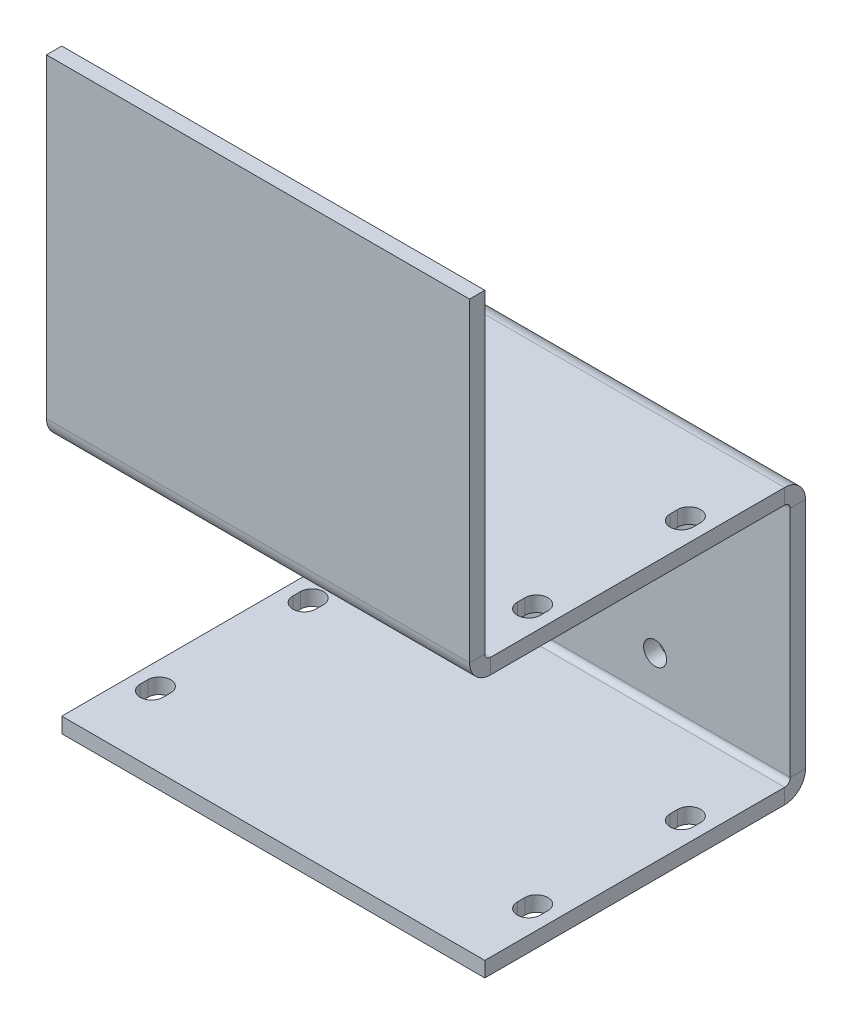
SolidWorks part; units mm, degrees
note: The reader was unsure of these and kept them because the rebuilt part matched: flange length of "Odgięcie krawędzi1", "Odgięcie krawędzi2".
ref_plane "Płaszczyzna przednia" through (0, 0, 0) normal (0, 0, 1) x (1, 0, 0)
ref_plane "Płaszczyzna górna" through (0, 0, 0) normal (0, 1, 0) x (1, 0, 0)
ref_plane "Płaszczyzna prawa" through (0, 0, 0) normal (1, 0, 0) x (0, 0, -1)
sketch "Szkic1" plane through (0, 0, 0) normal (0, 0, 1) x (1, 0, 0)
  line L1 (-27.7, -16) -> (27.7, -16)
  line L2 (-27.7, -16) -> (-27.7, 16)
  line L3 (-27.7, 16) -> (27.7, 16)
  line L4 (27.7, -16) -> (27.7, 16)
  line L5 (-27.7, -16) -> (27.7, 16) construction
  line L6 (-27.7, 16) -> (27.7, -16) construction
  point P0 (0, 0)
  dimension "D1" = 55.4
  dimension "D2" = 32
base flange "Odgięcie bazowe1" sketch "Szkic1" thickness 2 reverse thickness direction no parameters "D1"=0.7366
hole_wizard "Otwory ustalające Ø3.0mm1" positions "Szkic11" profile "Szkic12" hole size "Ø3.0" standard "Ansi Metric"
sketch "Szkic11" plane through (0, 0, -2) normal (0, 0, -1) x (-1, 0, 0)
  line L0 (0, 16) -> (0, -16) construction
  line L5 (-27.7, 0) -> (27.7, 0) construction
  line L6 (-27.7, -16) -> (-27.7, 16) construction
  line L7 (27.7, 16) -> (27.7, -16) construction
  line L11 (-27.7, 16) -> (27.7, 16) construction
  line L12 (27.7, -16) -> (-27.7, -16) construction
  point P0 (-10, 10)
  point P22 (10, 10)
  point P23 (10, -10)
  point P24 (-10, -10)
  dimension "D1" = 10
  dimension "D2" = 10
sketch "Szkic12" plane through (10, 10, -2) normal (1, 0, 0) x (0, 1, 0)
  line L0 (0, 0) -> (0, 17.9013)
  line L1 (0, 17.9013) -> (1.5, 17)
  line L2 (1.5, 17) -> (1.5, 0)
  line L5 (1.5, 0) -> (0, 0)
  line L10 (0, 17.9013) -> (-1.5, 17) construction
  line L11 (0, -6.35) -> (0, 107.95) construction
  dimension "Średnica otworu" = 3
  dimension "Głębokość otworu" = 17
  dimension "Kąt wiertła" = 118
edge flange "Odgięcie krawędzi1" sketch "Szkic8" flange profiles "Szkic8", "Szkic10" flange angle 90 flange length 42 flange position material outside bend radius 0.7366 thickness 2 relief rectangular parameters "D6"=10, "D8"=1
sketch "Szkic8" plane through (0, 16, 0) normal (0, 1, 0) x (-1, 0, 0)
  line L2 (-27.7, 0) -> (-27.7, 40)
  line L3 (-27.7, 40) -> (27.7, 40)
  line L4 (27.7, 40) -> (27.7, 0)
  line L7 (-27.7, 0) -> (27.7, 0) construction
  line L8 (-27.7, 0) -> (27.7, 0)
sketch "Szkic10" plane through (0, -16, 0) normal (0, -1, 0) x (1, 0, 0)
  line L0 (-27.7, 0) -> (27.7, 0) construction
  line L1 (-27.7, 0) -> (27.7, 0)
  line L2 (-27.7, 0) -> (-27.7, 40)
  line L3 (-27.7, 40) -> (27.7, 40)
  line L4 (27.7, 40) -> (27.7, 0)
bend "Zgięcie krawędziowe1" bend radius 0.7366 bend angle 90 parameters "D5"=1
bend "Zgięcie krawędziowe2" bend radius 0.7366 bend angle 90 parameters "D5"=3
edge flange "Odgięcie krawędzi2" sketch "Szkic15" flange angle 90 flange length 42 flange position material outside bend radius 0.7366 thickness 2 relief rectangular parameters "D6"=10
sketch "Szkic15" plane through (0, 18, 40) normal (0, 0, 1) x (1, 0, 0)
  line L0 (-27.7, 0) -> (27.7, 0) construction
  line L1 (-27.7, 0) -> (27.7, 0)
  line L2 (-27.7, 0) -> (-27.7, 42)
  line L3 (-27.7, 42) -> (27.7, 42)
  line L4 (27.7, 42) -> (27.7, 0)
bend "Zgięcie krawędziowe3" bend radius 0.7366 bend angle 90 parameters "D5"=4
sketch "Szkic16" plane through (0, 18, 0) normal (0, 1, 0) x (1, 0, 0)
  line L0 (0, 0) -> (0, -42) construction
  line L1 (27.7, -42) -> (-27.7, -42) construction
  line L2 (24.7, -30.2366) -> (24.7, -31.2366) construction
  line L3 (26.2, -30.2366) -> (26.2, -31.2366)
  line L4 (23.2, -30.2366) -> (23.2, -31.2366)
  line L5 (-27.7, -0.7366) -> (27.7, -0.7366) construction
  line L6 (27.7, -39.2634) -> (27.7, -0.7366) construction
  line L7 (24.7, -10.2366) -> (24.7, -11.2366) construction
  line L8 (26.2, -10.2366) -> (26.2, -11.2366)
  line L9 (23.2, -10.2366) -> (23.2, -11.2366)
  line L10 (-24.7, -10.2366) -> (-24.7, -11.2366) construction
  line L11 (-26.2, -10.2366) -> (-26.2, -11.2366)
  line L12 (-23.2, -10.2366) -> (-23.2, -11.2366)
  line L13 (-24.7, -30.2366) -> (-24.7, -31.2366) construction
  line L14 (-26.2, -30.2366) -> (-26.2, -31.2366)
  line L15 (-23.2, -30.2366) -> (-23.2, -31.2366)
  arc A0 (26.2, -30.2366) -> (23.2, -30.2366) centre (24.7, -30.2366) ccw
  arc A1 (23.2, -31.2366) -> (26.2, -31.2366) centre (24.7, -31.2366) ccw
  arc A2 (26.2, -10.2366) -> (23.2, -10.2366) centre (24.7, -10.2366) ccw
  arc A3 (23.2, -11.2366) -> (26.2, -11.2366) centre (24.7, -11.2366) ccw
  arc A4 (-26.2, -10.2366) -> (-23.2, -10.2366) centre (-24.7, -10.2366) cw
  arc A5 (-23.2, -11.2366) -> (-26.2, -11.2366) centre (-24.7, -11.2366) cw
  arc A6 (-26.2, -30.2366) -> (-23.2, -30.2366) centre (-24.7, -30.2366) cw
  arc A7 (-23.2, -31.2366) -> (-26.2, -31.2366) centre (-24.7, -31.2366) cw
  point P7 (24.7, -30.7366)
  point P17 (24.7, -10.7366)
  point P25 (-24.7, -10.7366)
  point P32 (-24.7, -30.7366)
  dimension "D1" = 3
  dimension "D2" = 1
  dimension "D3" = 30
  dimension "D4" = 3
  dimension "D5" = 10
  dimension "D6" = 3
  dimension "D7" = 1
  dimension "D8" = 3
extrude "Wytnij-wyciągnięcie1" cut sketch "Szkic16" against normal through all normal cut yes
sketch "Linie zgięcia1" [suppressed] plane through (0, 0, 0) normal (0, 1, 0) x (1, 0, 0)
sketch "Ramka-graniczna1" [suppressed] plane through (0, 0, 0) normal (0, 1, 0) x (1, 0, 0)
sheet metal parameters "Arkusz blachy1" thickness 2 parameters "D1"=0.7366
flat pattern "Rozłożony model1" [suppressed]
sketch "Linie zgięcia2" plane through (0, 0, 0) normal (0, 1, 0) x (1, 0, 0)
sketch3d "Ramka-graniczna2" [suppressed]
  line L0 (22.7, -14, 0) -> (-22.7, -14, 0) construction
  line L1 (22.7, 14, 0) -> (-22.7, 14, 0) construction
  line L2 (22.7, -14, 0) -> (22.7, 14, 0) construction
  line L3 (-22.7, -14, 0) -> (-22.7, 14, 0) construction
sheet metal parameters "Arkusz blachy2" thickness 2 parameters "D1"=0.7366
flat pattern "Rozłożony model1"
sketch "Linie zgięcia2" plane through (0, 0, 0) normal (0, 0, 1) x (1, 0, 0)
  line L0 (27.7, 16.6273) -> (-27.7, 16.6273) construction
  line L1 (27.7, 16.6273) -> (-27.7, 16.6273) construction
  line L2 (-27.7, -16.6273) -> (27.7, -16.6273) construction
  line L3 (-27.7, -16.6273) -> (27.7, -16.6273) construction
sketch3d "Ramka-graniczna2" [suppressed]
  line L0 (27.7, 57.2546, 0) -> (27.7, -57.2546, 0) construction
  line L1 (-27.7, 57.2546, 0) -> (-27.7, -57.2546, 0) construction
  line L2 (27.7, 57.2546, 0) -> (-27.7, 57.2546, 0) construction
  line L3 (27.7, -57.2546, 0) -> (-27.7, -57.2546, 0) construction
bend of the flat pattern "Rozłożone-<Zgięcie krawędziowe1>1"
bend of the flat pattern "Rozłożone-<Zgięcie krawędziowe2>1"
sheet metal parameters "Arkusz blachy3" thickness 2 parameters "D1"=0.7366
flat pattern "Rozłożony model1"
sketch "Linie zgięcia2" plane through (0, 0, 0) normal (0, 0, 1) x (1, 0, 0)
  line L0 (22.7, 14.6273) -> (-22.7, 14.6273) construction
  line L1 (22.7, 14.6273) -> (-22.7, 14.6273) construction
  line L2 (-22.7, -14.6273) -> (22.7, -14.6273) construction
  line L3 (-22.7, -14.6273) -> (22.7, -14.6273) construction
sketch3d "Ramka-graniczna2" [suppressed]
  line L0 (22.7, 58.2546, 0) -> (22.7, -58.2546, 0) construction
  line L1 (-22.7, 58.2546, 0) -> (-22.7, -58.2546, 0) construction
  line L2 (22.7, 58.2546, 0) -> (-22.7, 58.2546, 0) construction
  line L3 (22.7, -58.2546, 0) -> (-22.7, -58.2546, 0) construction
sheet metal parameters "Arkusz blachy4" thickness 2 parameters "D1"=0.7366
flat pattern "Rozłożony model1"
sketch "Linie zgięcia2" plane through (0, 0, 0) normal (0, 0, 1) x (1, 0, 0)
  line L0 (27.7, 16.6273) -> (-27.7, 16.6273) construction
  line L1 (27.7, 16.6273) -> (-27.7, 16.6273) construction
  line L2 (-27.7, -16.6273) -> (27.7, -16.6273) construction
  line L3 (-27.7, -16.6273) -> (27.7, -16.6273) construction
  line L4 (27.7, 57.882) -> (-27.7, 57.882) construction
  line L5 (27.7, 57.882) -> (-27.7, 57.882) construction
sketch3d "Ramka-graniczna2" [suppressed]
  line L0 (27.7, 100.5093, 0) -> (27.7, -57.2546, 0) construction
  line L1 (-27.7, 100.5093, 0) -> (-27.7, -57.2546, 0) construction
  line L2 (27.7, 100.5093, 0) -> (-27.7, 100.5093, 0) construction
  line L3 (27.7, -57.2546, 0) -> (-27.7, -57.2546, 0) construction
bend of the flat pattern "Rozłożone-<Zgięcie krawędziowe1>1"
bend of the flat pattern "Rozłożone-<Zgięcie krawędziowe2>1"
bend of the flat pattern "Rozłożone-<Zgięcie krawędziowe3>1"
sheet metal parameters "Arkusz blachy5" thickness 2 parameters "D1"=0.7366
flat pattern "Rozłożony model1"
sketch "Linie zgięcia2" plane through (0, 0, 0) normal (0, 0, 1) x (1, 0, 0)
  line L0 (27.7, 16.6273) -> (-27.7, 16.6273) construction
  line L1 (27.7, 16.6273) -> (-27.7, 16.6273) construction
  line L2 (-27.7, -16.6273) -> (27.7, -16.6273) construction
  line L3 (-27.7, -16.6273) -> (27.7, -16.6273) construction
  line L4 (27.7, 57.882) -> (-27.7, 57.882) construction
  line L5 (27.7, 57.882) -> (-27.7, 57.882) construction
sketch3d "Ramka-graniczna2" [suppressed]
  line L0 (27.7, 100.5093, 0) -> (27.7, -57.2546, 0) construction
  line L1 (-27.7, 100.5093, 0) -> (-27.7, -57.2546, 0) construction
  line L2 (27.7, 100.5093, 0) -> (-27.7, 100.5093, 0) construction
  line L3 (27.7, -57.2546, 0) -> (-27.7, -57.2546, 0) construction
bend of the flat pattern "Rozłożone-<Zgięcie krawędziowe1>1"
bend of the flat pattern "Rozłożone-<Zgięcie krawędziowe2>1"
bend of the flat pattern "Rozłożone-<Zgięcie krawędziowe3>1"
